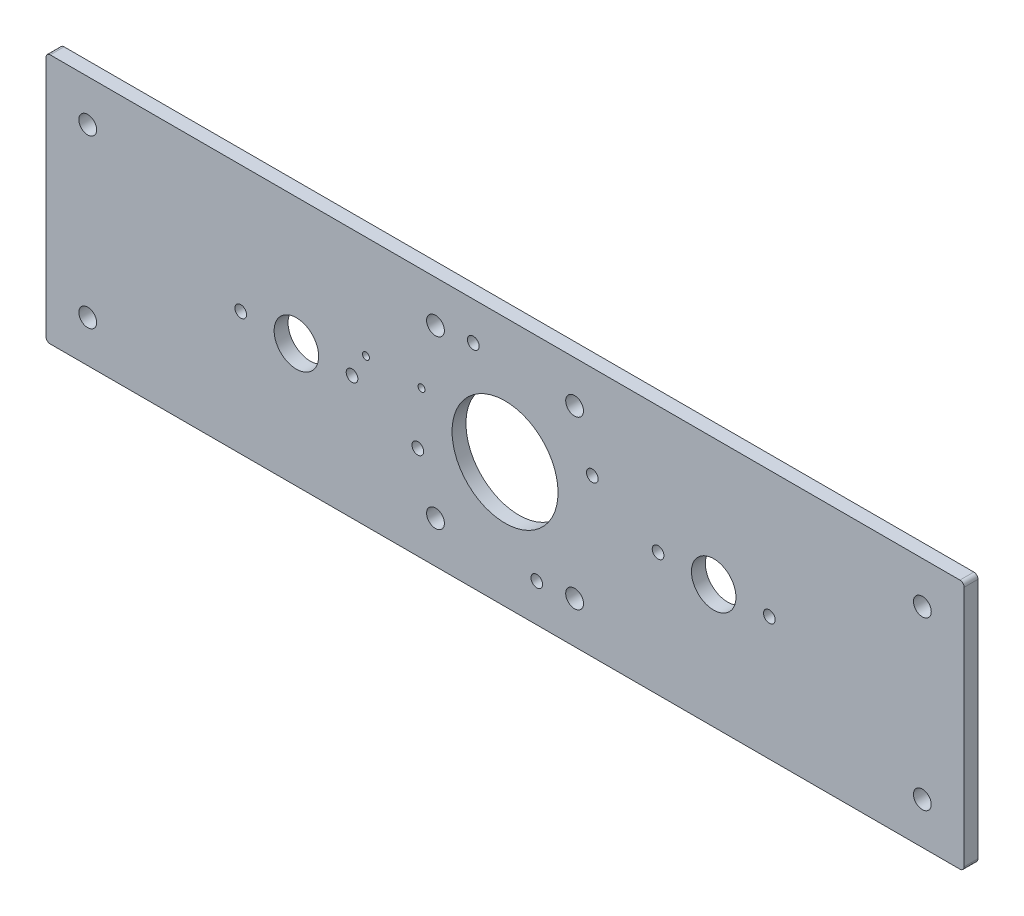
SolidWorks part; units mm, degrees
ref_plane "Front Plane" through (0, 0, 0) normal (0, 0, 1) x (1, 0, 0)
ref_plane "Top Plane" through (0, 0, 0) normal (0, 1, 0) x (1, 0, 0)
ref_plane "Right Plane" through (0, 0, 0) normal (1, 0, 0) x (0, 0, -1)
sketch "Sketch1" plane through (0, 0, 0) normal (0, 0, 1) x (1, 0, 0)
  line L1 (165, -45) -> (-165, -45)
  line L2 (165, -45) -> (165, 45)
  line L3 (165, 45) -> (-165, 45)
  line L4 (-165, -45) -> (-165, 45)
  line L5 (165, -45) -> (-165, 45) construction
  line L6 (165, 45) -> (-165, -45) construction
  circle A0 centre (0, 0) radius 19.05
  point P0 (0, 0)
  dimension "D3" = 38.1
  dimension "D1" = 90
  dimension "D2" = 330
extrude "Boss-Extrude1" add sketch "Sketch1" along normal mid plane 5
hole_wizard "M6 Clearance Hole1" positions "Sketch5" profile "Sketch4" hole size "M6" standard "ANSI Metric" end condition through all
sketch "Sketch5" plane through (0, 0, 2.5) normal (0, 0, 1) x (1, 0, 0)
  line L0 (165, 45) -> (-165, 45) construction
  line L1 (-165, 45) -> (-165, -45) construction
  line L2 (-165, -45) -> (165, -45) construction
  point P0 (-150, 30)
  point P2 (-25, 30)
  point P4 (-25, -30)
  point P6 (-150, -30)
  dimension "D1" = 15
  dimension "D2" = 25
  dimension "D3" = 15
  dimension "D4" = 15
  dimension "D5" = 15
  dimension "D6" = 15
  dimension "D7" = 15
  dimension "D8" = 25
sketch "Sketch4" plane through (-150, 30, 2.5) normal (1, 0, 0) x (0, -1, 0)
  line L0 (0, 0) -> (0, 5)
  line L1 (0, 5) -> (3.2, 5)
  line L2 (3.2, 5) -> (3.2, 0)
  line L5 (3.2, 0) -> (0, 0)
  line L11 (0, -6.35) -> (0, 107.95) construction
  dimension "Thru Hole Dia." = 6.4
  dimension "Thru Hole Depth" = 5
mirror "Mirror2" about plane through (0, 0, 0) normal (1, 0, 0) of "M6 Clearance Hole1"
sketch "Sketch3" plane through (0, 0, 2.5) normal (0, 0, 1) x (1, 0, 0)
  line L0 (0, -0.6) -> (-49.4534, -0.6) construction
  circle A2 centre (-75, -0.6) radius 8
  dimension "D3" = 16
  dimension "D4" = 75
  dimension "D7" = 0.6
extrude "Cut-Extrude2" cut sketch "Sketch3" against normal through all
hole_wizard "M5x0.8 Tapped Hole1" positions "Sketch7" profile "Sketch6" tap size "M5x0.8" standard "ANSI Metric" end condition through all
sketch "Sketch7" plane through (0, 0, 2.5) normal (0, 0, 1) x (1, 0, 0)
  line L0 (-1080, -0.6) -> (48920, -0.6) construction
  circle A0 centre (-75, -0.6) radius 8 construction
  point P0 (-95, -0.6)
  point P2 (-55, -0.6)
  dimension "D1" = 20
  dimension "D2" = 20
sketch "Sketch6" plane through (-95, -0.6, 2.5) normal (1, 0, 0) x (0, -1, 0)
  line L0 (0, 0) -> (0, 5)
  line L1 (0, 5) -> (2.1, 5)
  line L2 (2.1, 5) -> (2.1, 0)
  line L5 (2.1, 0) -> (0, 0)
  line L11 (0, -6.35) -> (0, 107.95) construction
  dimension "Thru Tap Drill Dia." = 4.2
  dimension "Thru Tap Drill Depth" = 5
cosmetic thread "Hole Thread1" parameters "D2"=5
cosmetic thread "Hole Thread2" parameters "D2"=5
mirror "Mirror1" about plane through (0, 0, 0) normal (1, 0, 0) of "M5x0.8 Tapped Hole1", "Cut-Extrude2"
hole_wizard "M5x0.8 Tapped Hole3" positions "Sketch9" profile "Sketch8" tap size "M5x0.8" standard "ANSI Metric" end condition through all
sketch "Sketch9" plane through (0, 0, 2.5) normal (0, 0, 1) x (1, 0, 0)
  line L1 (11.4151, -31.3627) -> (31.3627, 11.4151) construction
  line L2 (11.4151, -31.3627) -> (-31.3627, -11.4151) construction
  line L3 (-31.3627, -11.4151) -> (-11.4151, 31.3627) construction
  line L4 (31.3627, 11.4151) -> (-11.4151, 31.3627) construction
  line L5 (11.4151, -31.3627) -> (-11.4151, 31.3627) construction
  line L6 (-31.3627, -11.4151) -> (31.3627, 11.4151) construction
  line L7 (-1000, 0) -> (49000, 0) construction
  point P1 (-11.4151, 31.3627)
  point P164 (11.4151, -31.3627)
  point P165 (-31.3627, -11.4151)
  point P166 (31.3627, 11.4151)
  dimension "D1" = 47.2
  dimension "D2" = 47.2
  dimension "D3" = 110
  dimension "D4" = 90
  dimension "D5" = 90
  dimension "D6" = 90
  dimension "D7" = 23.6
  dimension "D8" = 23.6
sketch "Sketch8" plane through (-11.4151, 31.3627, 2.5) normal (1, 0, 0) x (0, -1, 0)
  line L0 (0, 0) -> (0, 5)
  line L1 (0, 5) -> (2.1, 5)
  line L2 (2.1, 5) -> (2.1, 0)
  line L5 (2.1, 0) -> (0, 0)
  line L11 (0, -6.35) -> (0, 107.95) construction
  dimension "Thru Tap Drill Dia." = 4.2
  dimension "Thru Tap Drill Depth" = 5
cosmetic thread "Hole Thread3" parameters "D2"=5
cosmetic thread "Hole Thread4" parameters "D2"=5
cosmetic thread "Hole Thread5" parameters "D2"=5
cosmetic thread "Hole Thread6" parameters "D2"=5
fillet "Fillet1" radius 1.5 4 edges at (-165, -45, 0) (165, -45, 0) (165, 45, 0) (-165, 45, 0)
hole_wizard "M3x0.5 Tapped Hole1" positions "Sketch12" profile "Sketch11" tap size "M3x0.5" standard "ANSI Metric" end condition through all
sketch "Sketch12" plane through (0, 0, 2.5) normal (0, 0, 1) x (1, 0, 0)
  line L0 (-50, 8) -> (-30, 8)
  point P0 (-50, 8)
  point P2 (-30, 8)
  dimension "D1" = 20
  dimension "D2" = 8
  dimension "D3" = 30
sketch "Sketch11" plane through (-50, 8, 2.5) normal (1, 0, 0) x (0, -1, 0)
  line L0 (0, 0) -> (0, 5)
  line L1 (0, 5) -> (1.25, 5)
  line L2 (1.25, 5) -> (1.25, 0)
  line L5 (1.25, 0) -> (0, 0)
  line L11 (0, -6.35) -> (0, 107.95) construction
  dimension "Thru Tap Drill Dia." = 2.5
  dimension "Thru Tap Drill Depth" = 5
cosmetic thread "Hole Thread7" parameters "D2"=3
cosmetic thread "Hole Thread8" parameters "D2"=3
equation "\"D4@Sketch3\"=150/2"
